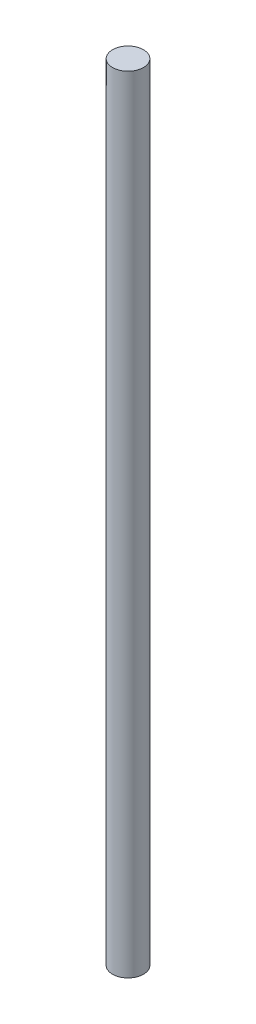
SolidWorks part; units mm, degrees
ref_plane "Front Plane" through (0, 0, 0) normal (0, 0, 1) x (1, 0, 0)
ref_plane "Top Plane" through (0, 0, 0) normal (0, 1, 0) x (1, 0, 0)
ref_plane "Right Plane" through (0, 0, 0) normal (1, 0, 0) x (0, 0, -1)
sketch "Sketch1" plane through (0, 0, 0) normal (0, 1, 0) x (1, 0, 0)
  circle A0 centre (0, 0) radius 6
extrude "Boss-Extrude1" add sketch "Sketch1" along normal blind 304.8
